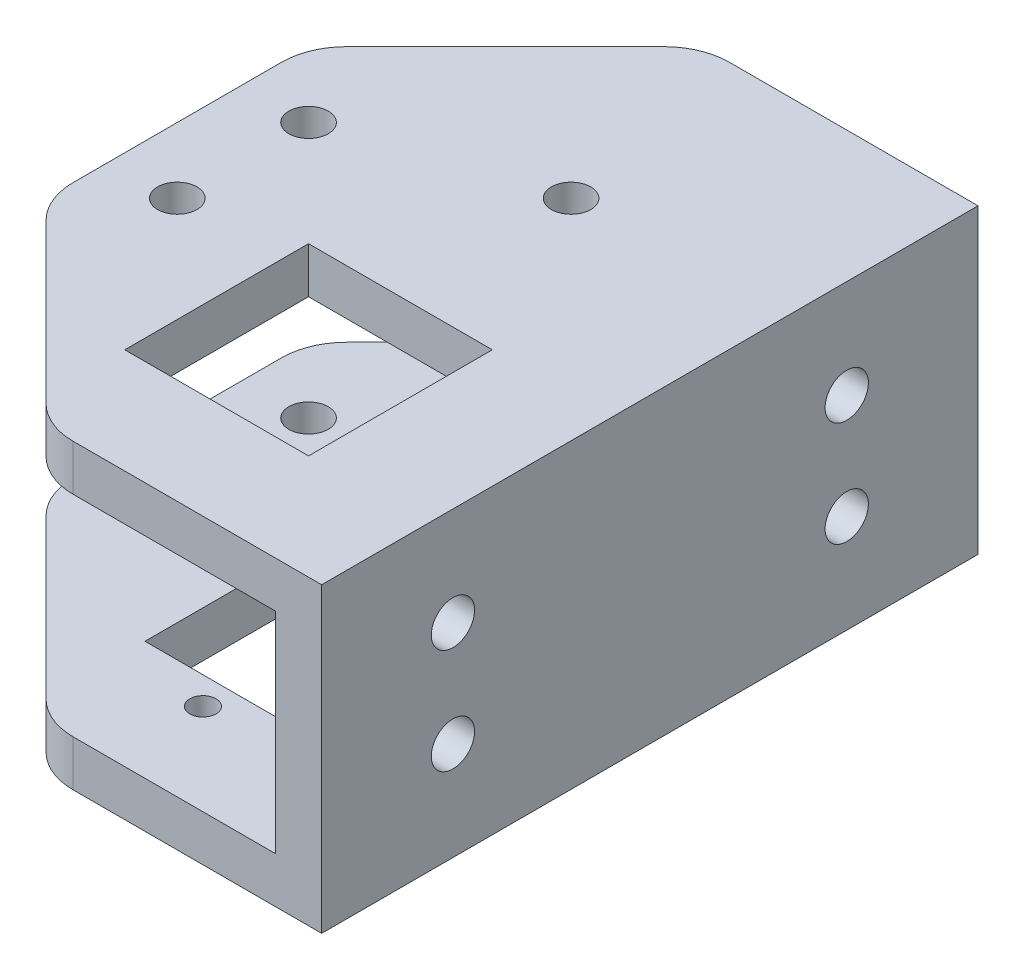
SolidWorks part; units mm, degrees
ref_plane "前视基准面" through (0, 0, 0) normal (0, 0, 1) x (1, 0, 0)
ref_plane "上视基准面" through (0, 0, 0) normal (0, 1, 0) x (1, 0, 0)
ref_plane "右视基准面" through (0, 0, 0) normal (1, 0, 0) x (0, 0, -1)
sketch "草图1" plane through (0, 0, 0) normal (0, 0, 1) x (1, 0, 0)
  line L0 (-45, 11.5) -> (0, 11.5)
  line L1 (0, 11.5) -> (0, -11.5)
  line L2 (0, -11.5) -> (-45, -11.5)
  line L3 (-45, 8) -> (-3.5, 8)
  line L4 (-3.5, 8) -> (-3.5, -8)
  line L5 (-3.5, -8) -> (-45, -8)
  line L6 (-45, 11.5) -> (-45, 8)
  line L7 (-45, -8) -> (-45, -11.5)
  dimension "D1" = 3.5
  dimension "D2" = 23
  dimension "D3" = 45
extrude "凸台-拉伸1" add sketch "草图1" along normal blind 50
sketch "草图2" plane through (0, -11.5, 0) normal (0, -1, 0) x (1, 0, 0)
  line L0 (0, 50) -> (0, 0) construction
  line L1 (-16, 25) -> (-40.6813, 25) construction
  line L2 (-16, 35) -> (-16, 50) construction
  line L3 (-45, 50) -> (0, 50) construction
  line L4 (-16, 15) -> (-16, 0) construction
  line L5 (-45, 0) -> (0, 0) construction
  circle A0 centre (-16, 35) radius 10 construction
  circle A1 centre (-16, 15) radius 10 construction
  circle A2 centre (-16, 35) radius 1.5
  circle A3 centre (-16, 15) radius 1.5
  circle A4 centre (-31, 30) radius 1.5
  circle A5 centre (-31, 20) radius 1.5
  dimension "D1" = 20
  dimension "D3" = 3
  dimension "D4" = 3
  dimension "D2" = 16
  dimension "D5" = 5
  dimension "D6" = 15
extrude "切除-拉伸1" cut sketch "草图2" against normal blind 70 from surface starting at face at (-24.25, 8, 25)
sketch "草图3" plane through (0, -11.5, 0) normal (0, -1, 0) x (1, 0, 0)
  line L0 (-21, 0) -> (-36, 15)
  line L1 (-45, 0) -> (0, 0) construction
  line L2 (-36, 15) -> (-36, 35)
  line L3 (-36, 35) -> (-21, 50)
  line L4 (-45, 50) -> (0, 50) construction
  line L6 (-40.6813, 25) -> (-23.9708, 25) construction
  line L7 (-21, 0) -> (0, 0)
  line L8 (0, 0) -> (0, 50)
  line L9 (0, 50) -> (-21, 50)
  dimension "D1" = 20
  dimension "D2" = 15
  dimension "D3" = 21
extrude "切除-拉伸2" cut sketch "草图3" against normal blind 70 flip side to cut
extrude "切除-拉伸4" cut sketch "草图2<3>" against normal blind 10 contours A4 | A5
sketch "草图2<3>" plane through (0, -11.5, 0) normal (0, -1, 0) x (1, 0, 0) same geometry as "草图2"
sketch "草图4" plane through (0, 11.5, 0) normal (0, 1, 0) x (1, 0, 0)
  line L0 (-16, -15.375) -> (-16, -43.045) construction
  circle A0 centre (-16, -35) radius 1.5 construction
  circle A1 centre (-16, -35) radius 1.5 construction
  dimension "D1" = 19.625
  dimension "D2" = 8.045
sketch "草图5" plane through (0, -11.5, 0) normal (0, -1, 0) x (1, 0, 0)
  line L0 (-16, 15.375) -> (-16, 43.045) construction
  line L1 (-16, 15.375) -> (-16, 43.045) construction
  circle A0 centre (-16, 43.045) radius 1
  circle A1 centre (-16, 15.375) radius 1
  dimension "D1" = 2
extrude "切除-拉伸5" cut sketch "草图5" against normal blind 10
fillet "圆角1" radius 5 8 edges at (-36, -9.75, 15) (-36, -9.75, 35) (-36, 9.75, 35) (-36, 9.75, 15) (-21, -9.75, 0) (-21, 9.75, 0) (-21, -9.75, 50) (-21, 9.75, 50)
sketch "草图6" plane through (0, -11.5, 0) normal (0, -1, 0) x (1, 0, 0)
  line L0 (-16, 15.375) -> (-16, 43.045) construction
  line L2 (-9.5, 17.46) -> (-22.5, 17.46)
  line L3 (-9.5, 17.46) -> (-9.5, 40.96)
  line L4 (-9.5, 40.96) -> (-22.5, 40.96)
  line L5 (-22.5, 17.46) -> (-22.5, 40.96)
  line L6 (-9.5, 17.46) -> (-22.5, 40.96) construction
  line L7 (-9.5, 40.96) -> (-22.5, 17.46) construction
  circle A0 centre (-16, 43.045) radius 1 construction
  circle A1 centre (-16, 43.045) radius 1 construction
  circle A2 centre (-16, 15.375) radius 1 construction
  circle A3 centre (-16, 15.375) radius 1 construction
  point P6 (-16, 29.21)
  dimension "D1" = 23.5
  dimension "D2" = 13
extrude "切除-拉伸6" cut sketch "草图6" against normal blind 10
sketch "草图7" plane through (0, 0, 0) normal (1, 0, 0) x (0, 0, -1)
  line L0 (0, 0) -> (-54.0378, 0) construction
  line L1 (-50, -11.5) -> (-50, 11.5) construction
  line L2 (0, -11.5) -> (0, 11.5) construction
  circle A0 centre (-10, 4) radius 1.65
  circle A1 centre (-40, 4) radius 1.65
  circle A2 centre (-10, -4) radius 1.65
  circle A3 centre (-40, -4) radius 1.65
  dimension "D1" = 3.3
  dimension "D2" = 10
  dimension "D3" = 10
  dimension "D4" = 4
extrude "切除-拉伸7" cut sketch "草图7" against normal blind 10
sketch "草图8" plane through (0, 11.5, 0) normal (0, 1, 0) x (1, 0, 0)
  line L1 (-23, -42) -> (-9, -42)
  line L2 (-23, -42) -> (-23, -28)
  line L3 (-23, -28) -> (-9, -28)
  line L4 (-9, -42) -> (-9, -28)
  line L5 (-23, -42) -> (-9, -28) construction
  line L6 (-23, -28) -> (-9, -42) construction
  circle A0 centre (-16, -35) radius 1.5 construction
  circle A1 centre (-16, -35) radius 1.5 construction
  dimension "D1" = 14
extrude "切除-拉伸8" cut sketch "草图8" against normal blind 10
